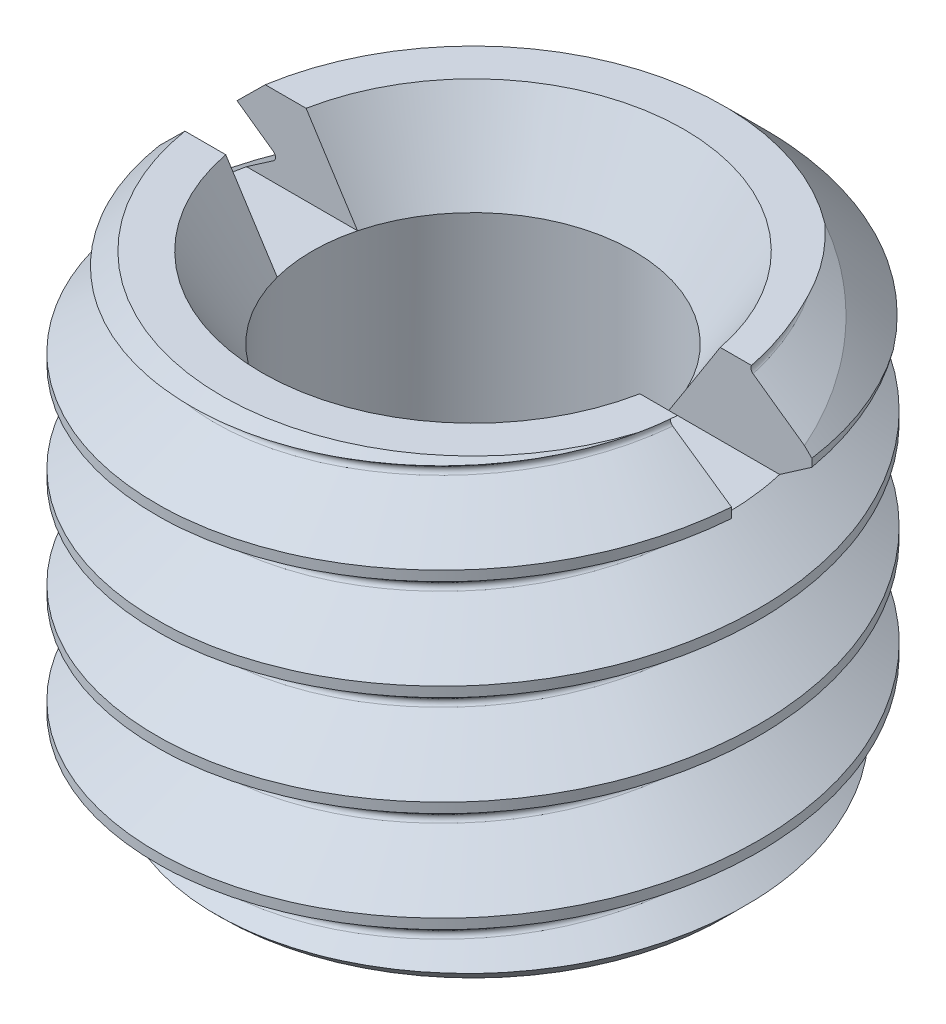
SolidWorks part; units mm, degrees
material "Brass"
ref_plane "Front Plane" through (0, 0, 0) normal (0, 0, 1) x (1, 0, 0)
ref_plane "Top Plane" through (0, 0, 0) normal (0, 1, 0) x (1, 0, 0)
ref_plane "Right Plane" through (0, 0, 0) normal (1, 0, 0) x (0, 0, -1)
sketch "Sketch1" plane through (0, 0, 0) normal (0, 0, 1) x (1, 0, 0)
  line L0 (0, 0) -> (0, 50.9753) construction
  line L1 (2.5, 4.5) -> (3, 4)
  line L2 (1.6, 0) -> (2.5, 0)
  line L3 (1.6, 0) -> (1.6, 3.7)
  line L4 (2.1, 4.5) -> (2.5, 4.5)
  line L5 (3, 0.5) -> (3, 4)
  line L6 (2.5, 0) -> (3, 0.5)
  line L7 (2.1, 4.5) -> (1.6, 3.7)
  point P4 (3, 4.5)
  point P6 (3, 0)
  dimension "D1" = 3.2
  dimension "D2" = 6
  dimension "D3" = 4.5
  dimension "D4" = 0.5
  dimension "D5" = 0.8
revolve "Revolve1" add sketch "Sketch1" angle 360 about L0
sketch "Sketch2" plane through (0, 4.5, 0) normal (0, 1, 0) x (1, 0, 0)
  circle A0 centre (0, 0) radius 3 construction
  circle A1 centre (0, 0) radius 3
curve "Helix/Spiral1" pitch 1 height 5.5 radius 3 centre (0, 4.5, 0) axis (0, -1, 0) start towards (0, 0, 1)
ref_plane "Plane1" through (-3, 4.5, 0) normal (0, -0.053, -0.9986) x (-1, 0, 0)
sketch "Sketch3" plane through (-3, 4.5, 0) normal (0, -0.053, -0.9986) x (-1, 0, 0)
  line L0 (0, 0) -> (0, 0.9)
  line L1 (0, 0.9) -> (-0.5789, 0.4908)
  line L2 (-0.5789, 0.4092) -> (0, 0)
  line L3 (-0.55, 0.45) -> (0, 0.45) construction
  arc A0 (-0.5789, 0.4908) -> (-0.5789, 0.4092) centre (-0.55, 0.45) ccw
  dimension "D2" = 0.05
  dimension "D3" = 0.6
  dimension "D1" = 0.9
sweep "Cut-Sweep1" cut profiles "Sketch3" path "Helix/Spiral1"
sketch "Sketch4" plane through (0, 4.5, 0) normal (0, 1, 0) x (1, 0, 0)
  line L0 (-4.6398, 0.4) -> (4.6398, -0.4) construction
  line L1 (-4.6398, 0.4) -> (4.6398, 0.4)
  line L2 (-4.6398, 0.4) -> (-4.6398, -0.4)
  line L3 (-4.6398, -0.4) -> (4.6398, -0.4)
  line L4 (4.6398, 0.4) -> (4.6398, -0.4)
  line L5 (4.6398, -0.4) -> (1.6849, -0.4332) construction
  dimension "D1" = 0.8
extrude "Cut-Extrude1" cut sketch "Sketch4" against normal blind 0.8
